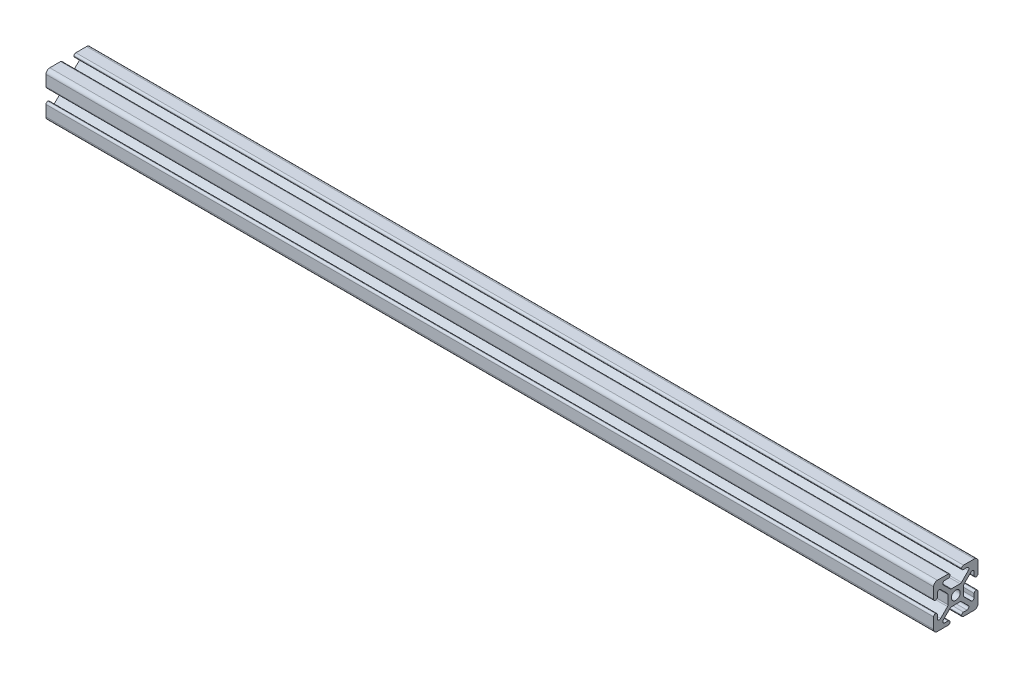
SolidWorks part; units mm, degrees
ref_plane "Front Plane" through (0, 0, 0) normal (1, 0, 0) x (0, 1, 0)
ref_plane "Top Plane" through (0, 0, 0) normal (0, 0, 1) x (0, 1, 0)
ref_plane "Right Plane" through (0, 0, 0) normal (0, 1, 0) x (-1, 0, 0)
sketch "Sketch1" plane through (0, 0, 0) normal (1, 0, 0) x (0, 1, 0)
  line L0 (0, 0) -> (0, 12.5) construction
  line L1 (-12.5, -12.5) -> (12.5, -12.5)
  line L2 (-12.5, -12.5) -> (-12.5, 12.5)
  line L3 (-12.5, 12.5) -> (12.5, 12.5)
  line L4 (12.5, -12.5) -> (12.5, 12.5)
  line L5 (-12.5, -12.5) -> (12.5, 12.5) construction
  line L6 (-12.5, 12.5) -> (12.5, -12.5) construction
  line L7 (-3.25, 12.5) -> (-3.25, 10.37)
  line L8 (-3.25, 10.37) -> (-8.8639, 10.37)
  line L9 (-8.8639, 10.37) -> (-2.8739, 4.38)
  line L10 (-2.8739, 4.38) -> (2.8739, 4.38)
  line L11 (8.8639, 10.37) -> (2.8739, 4.38)
  line L12 (3.25, 10.37) -> (8.8639, 10.37)
  line L13 (3.25, 12.5) -> (3.25, 10.37)
  line L14 (12.5, -3.25) -> (10.37, -3.25)
  line L15 (10.37, -3.25) -> (10.37, -8.8639)
  line L16 (10.37, -8.8639) -> (4.38, -2.8739)
  line L17 (4.38, 2.8739) -> (4.38, -2.8739)
  line L18 (10.37, 8.8639) -> (4.38, 2.8739)
  line L19 (10.37, 3.25) -> (10.37, 8.8639)
  line L20 (12.5, 3.25) -> (10.37, 3.25)
  line L21 (-3.25, -12.5) -> (-3.25, -10.37)
  line L22 (-3.25, -10.37) -> (-8.8639, -10.37)
  line L23 (-8.8639, -10.37) -> (-2.8739, -4.38)
  line L24 (2.8739, -4.38) -> (-2.8739, -4.38)
  line L25 (8.8639, -10.37) -> (2.8739, -4.38)
  line L26 (3.25, -10.37) -> (8.8639, -10.37)
  line L27 (3.25, -12.5) -> (3.25, -10.37)
  line L28 (-12.5, 3.25) -> (-10.37, 3.25)
  line L29 (-10.37, 3.25) -> (-10.37, 8.8639)
  line L30 (-10.37, 8.8639) -> (-4.38, 2.8739)
  line L31 (-4.38, -2.8739) -> (-4.38, 2.8739)
  line L32 (-10.37, -8.8639) -> (-4.38, -2.8739)
  line L33 (-10.37, -3.25) -> (-10.37, -8.8639)
  line L34 (-12.5, -3.25) -> (-10.37, -3.25)
  circle A0 centre (0, 0) radius 2.5
  point P0 (0, 0)
  point P15 (0, 4.38)
  dimension "D3" = 5
  dimension "D1" = 25
  dimension "D2" = 25
  dimension "D4" = 2.13
  dimension "D5" = 2.13
  dimension "D6" = 6.5
  dimension "D7" = 4.38
  dimension "D8" = 4
extrude "Boss-Extrude1" add sketch "Sketch1" along normal blind 500 contours L34 L2 L1 L21 L22 L23 L24 L25 L26 L27 L4 L14 L15 L16 L17 L18 L19 L20 L3 L13 L12 L11 L10 L9 L8 L7 L28 L29 L30 L31 L32 L33 A0 region at (0, -12.1464, -7.875)
fillet "Fillet1" radius 1.065 32 edges at (250, -10.37, -8.8639) (250, 2.8739, -4.38) (250, -2.8739, -4.38) (250, -4.38, 2.8739) (250, -4.38, -2.8739) (250, -2.8739, 4.38) (250, 2.8739, 4.38) (250, 4.38, 2.8739) (250, 4.38, -2.8739) (250, -8.8639, -10.37) (250, 8.8639, -10.37) (250, 10.37, -8.8639) (250, -10.37, 8.8639) (250, -8.8639, 10.37) (250, 10.37, 8.8639) (250, 8.8639, 10.37) (250, 12.5, 3.25) (250, -3.25, -12.5) (250, -10.37, 3.25) (250, 10.37, 3.25) (250, -10.37, -3.25) (250, -12.5, -3.25) (250, -12.5, 3.25) (250, 3.25, -10.37) (250, -3.25, -10.37) (250, 3.25, -12.5) (250, 10.37, -3.25) (250, 12.5, -3.25) (250, 3.25, 12.5) (250, 3.25, 10.37) (250, -3.25, 10.37) (250, -3.25, 12.5)
fillet "Fillet2" radius 2.13 4 edges at (250, 12.5, -12.5) (250, -12.5, -12.5) (250, 12.5, 12.5) (250, -12.5, 12.5)
sketch "Sketch2" plane through (500, 0, 0) normal (1, 0, 0) x (0, 1, 0)
  line L0 (10.37, -12.5) -> (4.315, -12.5)
  line L1 (10.37, -12.5) -> (4.315, -12.5)
  line L2 (4.315, -10.37) -> (6.2927, -10.37)
  line L3 (4.315, -10.37) -> (6.2927, -10.37)
  line L4 (7.0458, -8.5519) -> (3.1858, -4.6919)
  line L5 (7.0458, -8.5519) -> (3.1858, -4.6919)
  line L6 (2.4327, -4.38) -> (-2.4327, -4.38)
  line L7 (2.4327, -4.38) -> (-2.4327, -4.38)
  line L8 (-3.1858, -4.6919) -> (-7.0458, -8.5519)
  line L9 (-3.1858, -4.6919) -> (-7.0458, -8.5519)
  line L10 (-6.2927, -10.37) -> (-4.315, -10.37)
  line L11 (-6.2927, -10.37) -> (-4.315, -10.37)
  line L12 (-4.315, -12.5) -> (-10.37, -12.5)
  line L13 (-4.315, -12.5) -> (-10.37, -12.5)
  line L14 (-12.5, -10.37) -> (-12.5, -4.315)
  line L15 (-12.5, -10.37) -> (-12.5, -4.315)
  line L16 (-10.37, -4.315) -> (-10.37, -6.2927)
  line L17 (-10.37, -4.315) -> (-10.37, -6.2927)
  line L18 (-8.5519, -7.0458) -> (-4.6919, -3.1858)
  line L19 (-8.5519, -7.0458) -> (-4.6919, -3.1858)
  line L20 (-4.38, -2.4327) -> (-4.38, 2.4327)
  line L21 (-4.38, -2.4327) -> (-4.38, 2.4327)
  line L22 (-4.6919, 3.1858) -> (-8.5519, 7.0458)
  line L23 (-4.6919, 3.1858) -> (-8.5519, 7.0458)
  line L24 (-10.37, 6.2927) -> (-10.37, 4.315)
  line L25 (-10.37, 6.2927) -> (-10.37, 4.315)
  line L26 (-12.5, 4.315) -> (-12.5, 10.37)
  line L27 (-12.5, 4.315) -> (-12.5, 10.37)
  line L28 (-10.37, 12.5) -> (-4.315, 12.5)
  line L29 (-10.37, 12.5) -> (-4.315, 12.5)
  line L30 (-4.315, 10.37) -> (-6.2927, 10.37)
  line L31 (-4.315, 10.37) -> (-6.2927, 10.37)
  line L32 (-7.0458, 8.5519) -> (-3.1858, 4.6919)
  line L33 (-7.0458, 8.5519) -> (-3.1858, 4.6919)
  line L34 (-2.4327, 4.38) -> (2.4327, 4.38)
  line L35 (-2.4327, 4.38) -> (2.4327, 4.38)
  line L36 (3.1858, 4.6919) -> (7.0458, 8.5519)
  line L37 (3.1858, 4.6919) -> (7.0458, 8.5519)
  line L38 (6.2927, 10.37) -> (4.315, 10.37)
  line L39 (6.2927, 10.37) -> (4.315, 10.37)
  line L40 (4.315, 12.5) -> (10.37, 12.5)
  line L41 (4.315, 12.5) -> (10.37, 12.5)
  line L42 (12.5, 10.37) -> (12.5, 4.315)
  line L43 (12.5, 10.37) -> (12.5, 4.315)
  line L44 (10.37, 4.315) -> (10.37, 6.2927)
  line L45 (10.37, 4.315) -> (10.37, 6.2927)
  line L46 (8.5519, 7.0458) -> (4.6919, 3.1858)
  line L47 (8.5519, 7.0458) -> (4.6919, 3.1858)
  line L48 (4.38, 2.4327) -> (4.38, -2.4327)
  line L49 (4.38, 2.4327) -> (4.38, -2.4327)
  line L50 (4.6919, -3.1858) -> (8.5519, -7.0458)
  line L51 (4.6919, -3.1858) -> (8.5519, -7.0458)
  line L52 (10.37, -6.2927) -> (10.37, -4.315)
  line L53 (10.37, -6.2927) -> (10.37, -4.315)
  line L54 (12.5, -4.315) -> (12.5, -10.37)
  line L55 (12.5, -4.315) -> (12.5, -10.37)
  arc A0 (10.37, -12.5) -> (12.5, -10.37) centre (10.37, -10.37) ccw
  circle A1 centre (0, 0) radius 2.5
  circle A2 centre (0, 0) radius 2.5
  arc A3 (10.37, -12.5) -> (12.5, -10.37) centre (10.37, -10.37) ccw
  arc A4 (3.25, -11.435) -> (4.315, -12.5) centre (4.315, -11.435) ccw
  arc A5 (3.25, -11.435) -> (4.315, -12.5) centre (4.315, -11.435) ccw
  arc A6 (4.315, -10.37) -> (3.25, -11.435) centre (4.315, -11.435) ccw
  arc A7 (4.315, -10.37) -> (3.25, -11.435) centre (4.315, -11.435) ccw
  arc A8 (6.2927, -10.37) -> (7.0458, -8.5519) centre (6.2927, -9.305) ccw
  arc A9 (6.2927, -10.37) -> (7.0458, -8.5519) centre (6.2927, -9.305) ccw
  arc A10 (3.1858, -4.6919) -> (2.4327, -4.38) centre (2.4327, -5.445) ccw
  arc A11 (3.1858, -4.6919) -> (2.4327, -4.38) centre (2.4327, -5.445) ccw
  arc A12 (-2.4327, -4.38) -> (-3.1858, -4.6919) centre (-2.4327, -5.445) ccw
  arc A13 (-2.4327, -4.38) -> (-3.1858, -4.6919) centre (-2.4327, -5.445) ccw
  arc A14 (-7.0458, -8.5519) -> (-6.2927, -10.37) centre (-6.2927, -9.305) ccw
  arc A15 (-7.0458, -8.5519) -> (-6.2927, -10.37) centre (-6.2927, -9.305) ccw
  arc A16 (-3.25, -11.435) -> (-4.315, -10.37) centre (-4.315, -11.435) ccw
  arc A17 (-3.25, -11.435) -> (-4.315, -10.37) centre (-4.315, -11.435) ccw
  arc A18 (-4.315, -12.5) -> (-3.25, -11.435) centre (-4.315, -11.435) ccw
  arc A19 (-4.315, -12.5) -> (-3.25, -11.435) centre (-4.315, -11.435) ccw
  arc A20 (-12.5, -10.37) -> (-10.37, -12.5) centre (-10.37, -10.37) ccw
  arc A21 (-12.5, -10.37) -> (-10.37, -12.5) centre (-10.37, -10.37) ccw
  arc A22 (-11.435, -3.25) -> (-12.5, -4.315) centre (-11.435, -4.315) ccw
  arc A23 (-11.435, -3.25) -> (-12.5, -4.315) centre (-11.435, -4.315) ccw
  arc A24 (-10.37, -4.315) -> (-11.435, -3.25) centre (-11.435, -4.315) ccw
  arc A25 (-10.37, -4.315) -> (-11.435, -3.25) centre (-11.435, -4.315) ccw
  arc A26 (-10.37, -6.2927) -> (-8.5519, -7.0458) centre (-9.305, -6.2927) ccw
  arc A27 (-10.37, -6.2927) -> (-8.5519, -7.0458) centre (-9.305, -6.2927) ccw
  arc A28 (-4.6919, -3.1858) -> (-4.38, -2.4327) centre (-5.445, -2.4327) ccw
  arc A29 (-4.6919, -3.1858) -> (-4.38, -2.4327) centre (-5.445, -2.4327) ccw
  arc A30 (-4.38, 2.4327) -> (-4.6919, 3.1858) centre (-5.445, 2.4327) ccw
  arc A31 (-4.38, 2.4327) -> (-4.6919, 3.1858) centre (-5.445, 2.4327) ccw
  arc A32 (-8.5519, 7.0458) -> (-10.37, 6.2927) centre (-9.305, 6.2927) ccw
  arc A33 (-8.5519, 7.0458) -> (-10.37, 6.2927) centre (-9.305, 6.2927) ccw
  arc A34 (-11.435, 3.25) -> (-10.37, 4.315) centre (-11.435, 4.315) ccw
  arc A35 (-11.435, 3.25) -> (-10.37, 4.315) centre (-11.435, 4.315) ccw
  arc A36 (-12.5, 4.315) -> (-11.435, 3.25) centre (-11.435, 4.315) ccw
  arc A37 (-12.5, 4.315) -> (-11.435, 3.25) centre (-11.435, 4.315) ccw
  arc A38 (-10.37, 12.5) -> (-12.5, 10.37) centre (-10.37, 10.37) ccw
  arc A39 (-10.37, 12.5) -> (-12.5, 10.37) centre (-10.37, 10.37) ccw
  arc A40 (-3.25, 11.435) -> (-4.315, 12.5) centre (-4.315, 11.435) ccw
  arc A41 (-3.25, 11.435) -> (-4.315, 12.5) centre (-4.315, 11.435) ccw
  arc A42 (-4.315, 10.37) -> (-3.25, 11.435) centre (-4.315, 11.435) ccw
  arc A43 (-4.315, 10.37) -> (-3.25, 11.435) centre (-4.315, 11.435) ccw
  arc A44 (-6.2927, 10.37) -> (-7.0458, 8.5519) centre (-6.2927, 9.305) ccw
  arc A45 (-6.2927, 10.37) -> (-7.0458, 8.5519) centre (-6.2927, 9.305) ccw
  arc A46 (-3.1858, 4.6919) -> (-2.4327, 4.38) centre (-2.4327, 5.445) ccw
  arc A47 (-3.1858, 4.6919) -> (-2.4327, 4.38) centre (-2.4327, 5.445) ccw
  arc A48 (2.4327, 4.38) -> (3.1858, 4.6919) centre (2.4327, 5.445) ccw
  arc A49 (2.4327, 4.38) -> (3.1858, 4.6919) centre (2.4327, 5.445) ccw
  arc A50 (7.0458, 8.5519) -> (6.2927, 10.37) centre (6.2927, 9.305) ccw
  arc A51 (7.0458, 8.5519) -> (6.2927, 10.37) centre (6.2927, 9.305) ccw
  arc A52 (3.25, 11.435) -> (4.315, 10.37) centre (4.315, 11.435) ccw
  arc A53 (3.25, 11.435) -> (4.315, 10.37) centre (4.315, 11.435) ccw
  arc A54 (4.315, 12.5) -> (3.25, 11.435) centre (4.315, 11.435) ccw
  arc A55 (4.315, 12.5) -> (3.25, 11.435) centre (4.315, 11.435) ccw
  arc A56 (12.5, 10.37) -> (10.37, 12.5) centre (10.37, 10.37) ccw
  arc A57 (12.5, 10.37) -> (10.37, 12.5) centre (10.37, 10.37) ccw
  arc A58 (11.435, 3.25) -> (12.5, 4.315) centre (11.435, 4.315) ccw
  arc A59 (11.435, 3.25) -> (12.5, 4.315) centre (11.435, 4.315) ccw
  arc A60 (10.37, 4.315) -> (11.435, 3.25) centre (11.435, 4.315) ccw
  arc A61 (10.37, 4.315) -> (11.435, 3.25) centre (11.435, 4.315) ccw
  arc A62 (10.37, 6.2927) -> (8.5519, 7.0458) centre (9.305, 6.2927) ccw
  arc A63 (10.37, 6.2927) -> (8.5519, 7.0458) centre (9.305, 6.2927) ccw
  arc A64 (4.6919, 3.1858) -> (4.38, 2.4327) centre (5.445, 2.4327) ccw
  arc A65 (4.6919, 3.1858) -> (4.38, 2.4327) centre (5.445, 2.4327) ccw
  arc A66 (4.38, -2.4327) -> (4.6919, -3.1858) centre (5.445, -2.4327) ccw
  arc A67 (4.38, -2.4327) -> (4.6919, -3.1858) centre (5.445, -2.4327) ccw
  arc A68 (8.5519, -7.0458) -> (10.37, -6.2927) centre (9.305, -6.2927) ccw
  arc A69 (8.5519, -7.0458) -> (10.37, -6.2927) centre (9.305, -6.2927) ccw
  arc A70 (11.435, -3.25) -> (10.37, -4.315) centre (11.435, -4.315) ccw
  arc A71 (11.435, -3.25) -> (10.37, -4.315) centre (11.435, -4.315) ccw
  arc A72 (12.5, -4.315) -> (11.435, -3.25) centre (11.435, -4.315) ccw
  arc A73 (12.5, -4.315) -> (11.435, -3.25) centre (11.435, -4.315) ccw
  dimension "D1" = 0
